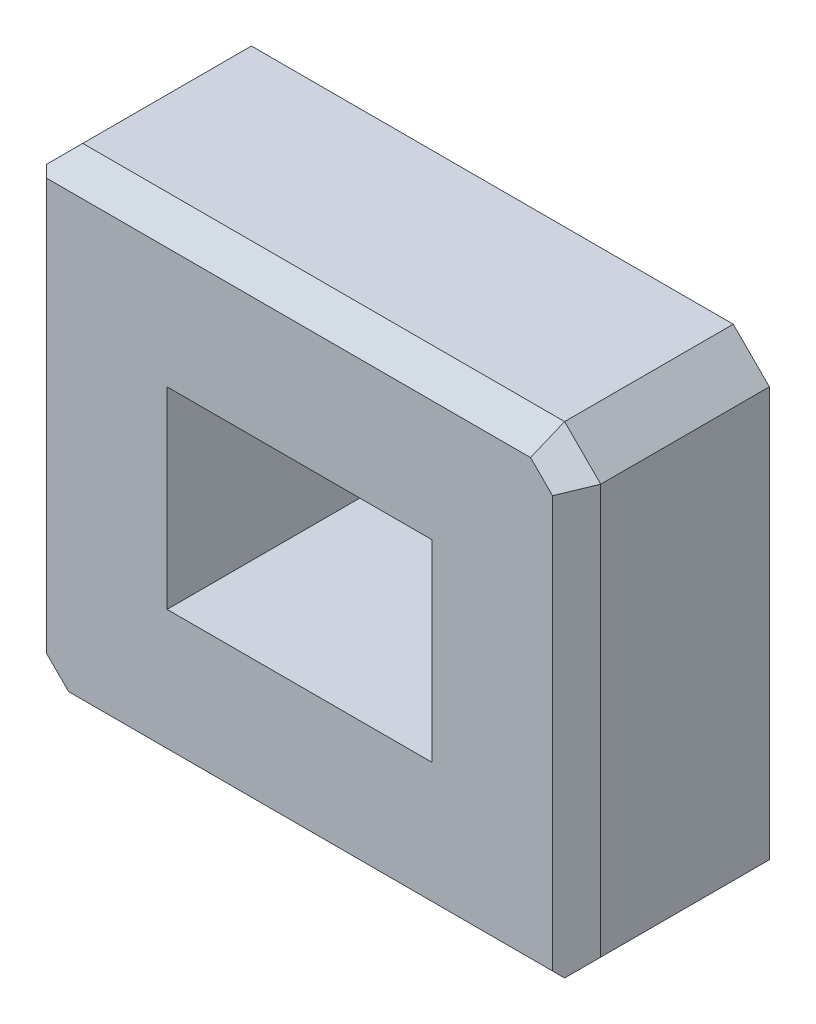
SolidWorks part; units mm, degrees
ref_plane "Alzado" through (0, 0, 0) normal (0, 0, 1) x (1, 0, 0)
ref_plane "Planta" through (0, 0, 0) normal (0, 1, 0) x (1, 0, 0)
ref_plane "Vista lateral" through (0, 0, 0) normal (1, 0, 0) x (0, 0, -1)
sketch "Croquis1" plane through (0, 0, 0) normal (0, 0, 1) x (1, 0, 0)
  line L0 (-11.5, 8.5) -> (-10, 10)
  line L1 (-10, -10) -> (10, -10)
  line L2 (-11.5, -8.5) -> (-11.5, 8.5)
  line L3 (-10, 10) -> (10, 10)
  line L4 (11.5, -8.5) -> (11.5, 8.5)
  line L5 (-11.5, -10) -> (11.5, 10) construction
  line L6 (-11.5, 10) -> (11.5, -10) construction
  line L7 (10, 10) -> (11.5, 8.5)
  line L8 (10, -10) -> (11.5, -8.5)
  line L9 (-11.5, -8.5) -> (-10, -10)
  point P0 (0, 0)
  dimension "D1" = 23
  dimension "D2" = 20
extrude "Saliente-Extruir1" add sketch "Croquis1" along normal blind 8
sketch "Croquis2" plane through (0, 0, 8) normal (0, 0, 1) x (1, 0, 0)
  line L1 (-5.5, -4) -> (5.5, -4)
  line L2 (-5.5, -4) -> (-5.5, 4)
  line L3 (-5.5, 4) -> (5.5, 4)
  line L4 (5.5, -4) -> (5.5, 4)
  line L5 (-5.5, -4) -> (5.5, 4) construction
  line L6 (-5.5, 4) -> (5.5, -4) construction
  point P0 (0, 0)
  dimension "D1" = 11
  dimension "D2" = 8
extrude "Cortar-Extruir1" cut sketch "Croquis2" against normal through all
chamfer "Chaflán1" distance 1 angle 45 6 edges at (-11.5, 0, 8) (-10.75, -9.25, 8) (0, -10, 8) (11.5, 0, 8) (10.75, 9.25, 8) (0, 10, 8)
